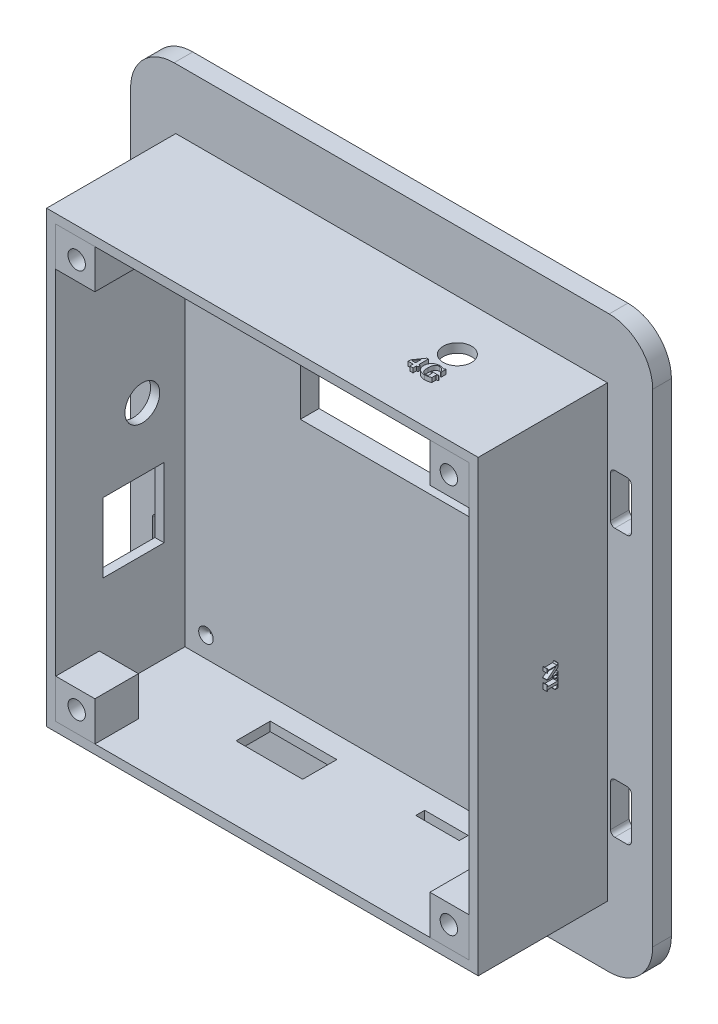
SolidWorks part; units mm, degrees
ref_plane "Front Plane" through (0, 0, 0) normal (0, 0, 1) x (1, 0, 0)
ref_plane "Top Plane" through (0, 0, 0) normal (0, 1, 0) x (1, 0, 0)
ref_plane "Right Plane" through (0, 0, 0) normal (1, 0, 0) x (0, 0, -1)
sketch "Sketch1" plane through (0, 0, 0) normal (0, 0, 1) x (1, 0, 0)
  line L1 (-60, -65.5) -> (60, -65.5)
  line L2 (-60, -65.5) -> (-60, 65.5)
  line L3 (-60, 65.5) -> (60, 65.5)
  line L4 (60, -65.5) -> (60, 65.5)
  line L5 (-60, -65.5) -> (60, 65.5) construction
  line L6 (-60, 65.5) -> (60, -65.5) construction
  point P0 (0, 0)
  dimension "D1" = 120
  dimension "D2" = 131
extrude "Boss-Extrude1" add sketch "Sketch1" along normal blind 4.3
fillet "Fillet1" radius 10 4 edges at (60, 65.5, 2.15) (60, -65.5, 2.15) (-60, -65.5, 2.15) (-60, 65.5, 2.15)
sketch "Sketch4" plane through (0, 0, 0) normal (0, 0, 1) x (1, 0, 0)
  line L0 (50, 65.5) -> (-50, 65.5) construction
  line L1 (-20.98, 43.63) -> (20.89, 43.63)
  line L2 (-20.98, 43.63) -> (-20.98, 9.03)
  line L3 (-20.98, 9.03) -> (20.89, 9.03)
  line L4 (20.89, 43.63) -> (20.89, 9.03)
  line L5 (-20.98, 43.63) -> (20.89, 9.03) construction
  line L6 (-20.98, 9.03) -> (20.89, 43.63) construction
  line L7 (-60, 55.5) -> (-60, -55.5) construction
  point P0 (-0.045, 26.33)
  dimension "D1" = 41.87
  dimension "D2" = 34.6
  dimension "D3" = 21.87
  dimension "D4" = 39.02
extrude "Cut-Extrude1" cut sketch "Sketch4" along normal up to surface (4.3 mm away) up to face at (0, 0, 4.3)
sketch "Sketch5" plane through (0, 0, 0) normal (0, 0, 1) x (1, 0, 0)
  line L0 (-60, 55.5) -> (-60, -55.5) construction
  line L1 (-55, 35) -> (-50.2, 35)
  line L2 (-55, 35) -> (-55, 23.5)
  line L3 (-55, 23.5) -> (-50.2, 23.5)
  line L4 (-50.2, 35) -> (-50.2, 23.5)
  line L5 (-55, 35) -> (-50.2, 23.5) construction
  line L6 (-55, 23.5) -> (-50.2, 35) construction
  line L7 (50, 65.5) -> (-50, 65.5) construction
  line L10 (-20.98, 9.03) -> (-20.98, 43.63) construction
  point P0 (-52.6, 29.25)
  dimension "D1" = 11.5
  dimension "D2" = 4.8
  dimension "D3" = 5
  dimension "D4" = 30.5
  dimension "D5" = 29.22
extrude "Cut-Extrude3" cut sketch "Sketch5" along normal up to surface (4.3 mm away) up to face at (0, 0, 4.3)
sketch "Sketch6" plane through (0, 0, 0) normal (0, 0, 1) x (1, 0, 0)
  line L1 (-55, -26.5) -> (-50.2, -26.5)
  line L2 (-55, -26.5) -> (-55, -38)
  line L3 (-55, -38) -> (-50.2, -38)
  line L4 (-50.2, -26.5) -> (-50.2, -38)
  line L5 (-55, -26.5) -> (-50.2, -38) construction
  line L6 (-55, -38) -> (-50.2, -26.5) construction
  line L7 (-60, 55.5) -> (-60, -55.5) construction
  line L8 (-50.2, 23.5) -> (-55, 23.5) construction
  point P0 (-52.6, -32.25)
  dimension "D1" = 11.5
  dimension "D2" = 4.8
  dimension "D3" = 5
  dimension "D4" = 50
extrude "Cut-Extrude4" cut sketch "Sketch6" along normal up to surface (4.3 mm away) up to face at (-0.045, 26.33, 4.3)
sketch "Sketch7" plane through (0, 0, 0) normal (0, 0, 1) x (1, 0, 0)
  line L1 (50.3, 35) -> (55.1, 35)
  line L2 (50.3, 35) -> (50.3, 23.5)
  line L3 (50.3, 23.5) -> (55.1, 23.5)
  line L4 (55.1, 35) -> (55.1, 23.5)
  line L5 (50.3, 35) -> (55.1, 23.5) construction
  line L6 (50.3, 23.5) -> (55.1, 35) construction
  line L9 (50, 65.5) -> (-50, 65.5) construction
  line L10 (60, -55.5) -> (60, 55.5) construction
  point P0 (52.7, 29.25)
  point P7 (52.7, 35)
  dimension "D1" = 4.8
  dimension "D2" = 11.5
  dimension "D3" = 30.5
  dimension "D4" = 4.9
extrude "Cut-Extrude5" cut sketch "Sketch7" along normal up to surface (4.3 mm away) up to face at (-52.6, 29.25, 4.3)
sketch "Sketch8" plane through (0, 0, 0) normal (0, 0, 1) x (1, 0, 0)
  line L0 (60, -55.5) -> (60, 55.5) construction
  line L1 (50.3, -26.5) -> (55.1, -26.5)
  line L2 (50.3, -26.5) -> (50.3, -38)
  line L3 (50.3, -38) -> (55.1, -38)
  line L4 (55.1, -26.5) -> (55.1, -38)
  line L5 (50.3, -26.5) -> (55.1, -38) construction
  line L6 (50.3, -38) -> (55.1, -26.5) construction
  line L7 (55.1, 23.5) -> (50.3, 23.5) construction
  point P0 (52.7, -32.25)
  dimension "D1" = 4.8
  dimension "D2" = 11.5
  dimension "D3" = 4.9
  dimension "D4" = 50
extrude "Cut-Extrude6" cut sketch "Sketch8" along normal up to surface (4.3 mm away) up to face at (-52.6, -32.25, 4.3)
sketch "Sketch18" plane through (0, 0, 0) normal (0, 0, 1) x (1, 0, 0)
  line L1 (49.5, -51.5) -> (-49.5, -51.5)
  line L2 (49.5, -51.5) -> (49.5, 51.5)
  line L3 (49.5, 51.5) -> (-49.5, 51.5)
  line L4 (-49.5, -51.5) -> (-49.5, 51.5)
  line L5 (49.5, -51.5) -> (-49.5, 51.5) construction
  line L6 (49.5, 51.5) -> (-49.5, -51.5) construction
  point P0 (0, 0)
  dimension "D1" = 99
  dimension "D2" = 103
extrude "Extrude-Thin2" add sketch "Sketch18" along normal blind 34 thin thin type two direction wall 0.1 second wall 2
sketch "Sketch26" plane through (0, 0, 0) normal (0, 0, 1) x (1, 0, 0)
  line L0 (20.89, 43.63) -> (20.89, 9.03) construction
  circle A0 centre (25.89, 44.0116) radius 3.5333
  dimension "D1" = 5
extrude "Boss-Extrude9" add sketch "Sketch26" along normal offset from surface (0.3 mm away) 4 up to face at (0, 0, 4.3)
sketch "Sketch28" plane through (0, 0, 0) normal (1, 0, 0) x (0, 0, -1)
  line L0 (-4.3, 51.6) -> (-4.3, -51.6) construction
  line L1 (-9.1, -10.4) -> (-23.1, -10.4)
  line L2 (-9.1, -10.4) -> (-9.1, -26.4)
  line L3 (-9.1, -26.4) -> (-23.1, -26.4)
  line L4 (-23.1, -10.4) -> (-23.1, -26.4)
  line L5 (-9.1, -10.4) -> (-23.1, -26.4) construction
  line L6 (-9.1, -26.4) -> (-23.1, -10.4) construction
  line L7 (-34, 51.6) -> (-4.3, 51.6) construction
  point P0 (-16.1, -18.4)
  dimension "D1" = 14
  dimension "D2" = 16
  dimension "D3" = 4.8
  dimension "D4" = 62
extrude "Cut-Extrude24" cut sketch "Sketch28" against normal up to surface (49.6 mm away) up to face at (-49.6, 0, 19.15)
sketch "Sketch29" plane through (0, 0, 0) normal (1, 0, 0) x (0, 0, -1)
  line L0 (-4.3, 55.5) -> (-4.3, -55.5) construction
  circle A0 centre (-14.1, 3.9508) radius 4
  dimension "D1" = 9.8
extrude "Cut-Extrude26" cut sketch "Sketch29" against normal up to surface (49.6 mm away) up to face at (-49.6, -18.4, 16.1)
sketch "Sketch30" plane through (0, 0, 0) normal (0, 1, 0) x (1, 0, 0)
  line L0 (49.6, -34) -> (49.6, -4.3) construction
  line L1 (-7.6, -9.3) -> (-22.9, -9.3)
  line L2 (-7.6, -9.3) -> (-7.6, -17.15)
  line L3 (-7.6, -17.15) -> (-22.9, -17.15)
  line L4 (-22.9, -9.3) -> (-22.9, -17.15)
  line L5 (-7.6, -9.3) -> (-22.9, -17.15) construction
  line L6 (-7.6, -17.15) -> (-22.9, -9.3) construction
  line L7 (-49.6, -4.3) -> (49.6, -4.3) construction
  point P0 (-15.25, -13.225)
  dimension "D1" = 15.3
  dimension "D2" = 7.85
  dimension "D3" = 57.2
  dimension "D4" = 5
extrude "Cut-Extrude27" cut sketch "Sketch30" against normal up to surface (51.6 mm away) up to face at (0, -51.6, 19.15)
sketch "Sketch31" plane through (0, 0, 0) normal (0, 1, 0) x (1, 0, 0)
  line L0 (-50, -4.3) -> (50, -4.3) construction
  line L1 (22.6, -9.3) -> (12.6, -9.3)
  line L2 (22.6, -9.3) -> (22.6, -11.35)
  line L3 (22.6, -11.35) -> (12.6, -11.35)
  line L4 (12.6, -9.3) -> (12.6, -11.35)
  line L5 (22.6, -9.3) -> (12.6, -11.35) construction
  line L6 (22.6, -11.35) -> (12.6, -9.3) construction
  line L7 (49.6, -34) -> (49.6, -4.3) construction
  point P0 (17.6, -10.325)
  point P7 (17.6, -9.3)
  point P10 (22.6, -10.325)
  dimension "D1" = 10
  dimension "D2" = 2.05
  dimension "D3" = 5
  dimension "D4" = 27
extrude "Cut-Extrude28" cut sketch "Sketch31" against normal up to surface (51.6 mm away) up to face at (-15.25, -51.6, 13.225)
sketch "Sketch35" plane through (0, -51.6, 0) normal (0, -1, 0) x (-1, 0, 0)
  text T0 "<b>USB</b>" font "Times New Roman" height 4
extrude "Boss-Extrude17" add sketch "Sketch35" along normal blind 1
sketch "Sketch38" plane through (0, -51.6, 0) normal (0, -1, 0) x (-1, 0, 0)
  line L0 (-21.1509, -16.35) -> (-12.6509, -16.35)
  line L1 (-12.6509, -16.35) -> (-12.6509, -26.35)
  line L2 (-12.6509, -26.35) -> (-25.6509, -26.35)
  line L3 (-25.6509, -26.35) -> (-25.6509, -19.35)
  line L4 (-25.6509, -19.35) -> (-21.1509, -16.35)
  line L5 (-22.6, -11.35) -> (-12.6, -11.35) construction
  dimension "D1" = 8.5
  dimension "D2" = 10
  dimension "D3" = 13
  dimension "D4" = 7
  dimension "D5" = 5
extrude "Boss-Extrude23" add sketch "Sketch38" along normal blind 1
sketch "Sketch39" plane through (0, -51.6, 0) normal (0, -1, 0) x (-1, 0, 0)
  text T0 "<b>SIM</b>" font "Times New Roman" height 3.5
extrude "Boss-Extrude30" add sketch "Sketch39" along normal blind 1 separate body
sketch "Sketch54" plane through (0, 0, 0) normal (0, 1, 0) x (1, 0, 0)
  line L2 (50, -4.3) -> (-50, -4.3) construction
  circle A0 centre (26.6908, -15.875) radius 3.25
  dimension "D1" = 11.575
extrude "Cut-Extrude31" cut sketch "Sketch54" along normal up to surface (51.6 mm away) up to face at (0, 51.6, 19.15)
sketch "Sketch55" plane through (0, 51.6, 0) normal (0, 1, 0) x (1, 0, 0)
  text T0 "4G" font "Times New Roman" height 3.5
extrude "Boss-Extrude32" add sketch "Sketch55" along normal blind 1 separate body
sketch "Sketch58" plane through (49.6, 0, 0) normal (1, 0, 0) x (0, 0, -1)
  line L5 (-19.125, 51.6) -> (-19.15, -51.6) construction
  line L6 (-34, -51.6) -> (-4.3, -51.6) construction
  text T0 "<b>NT</b>" font "Times New Roman" height 2.5
extrude "Boss-Extrude34" add sketch "Sketch58" along normal blind 1
sketch "Sketch59" plane through (-49.6, 0, 0) normal (-1, 0, 0) x (0, 0, 1)
  line L0 (27.1425, -51.6) -> (27.1425, 51.6) construction
  line L1 (34, -51.6) -> (4.3, -51.6) construction
  line L2 (34, 51.6) -> (4.3, 51.6) construction
  text T0 "                     LAN" font "Times New Roman" height 3.5
extrude "Boss-Extrude35" add sketch "Sketch59" along normal blind 1
fillet "Fillet4" radius 1 4 edges at (50.3, 35, 2.15) (50.3, 23.5, 2.15) (55.1, 23.5, 2.15) (55.1, 35, 2.15)
fillet "Fillet5" radius 1 4 edges at (50.3, -26.5, 2.15) (50.3, -38, 2.15) (55.1, -38, 2.15) (55.1, -26.5, 2.15)
fillet "Fillet7" radius 1 4 edges at (-55, -38, 2.15) (-50.2, -38, 2.15) (-50.2, -26.5, 2.15) (-55, -26.5, 2.15)
sketch "Sketch61" plane through (0, 0, 4.3) normal (0, 0, 1) x (1, 0, 0)
  line L0 (-47.5, 49.5) -> (-47.5, -49.5) construction
  line L1 (-47.5, -40.5) -> (-38.5, -40.5)
  line L2 (-47.5, -40.5) -> (-47.5, -49.5)
  line L3 (-47.5, -49.5) -> (-38.5, -49.5)
  line L4 (-38.5, -40.5) -> (-38.5, -49.5)
  line L5 (-47.5, -40.5) -> (-38.5, -49.5) construction
  line L6 (-47.5, -49.5) -> (-38.5, -40.5) construction
  line L7 (-47.5, -49.5) -> (47.5, -49.5) construction
  point P0 (-43, -45)
  point P7 (-43, -49.5)
  dimension "D1" = 0
  dimension "D2" = 0
  dimension "D3" = 9
  dimension "D4" = 9
extrude "Boss-Extrude37" add sketch "Sketch61" along normal blind 10 from offset 19.7 separate body
sketch "Sketch62" plane through (0, 0, 4.3) normal (0, 0, 1) x (1, 0, 0)
  line L0 (47.5, 49.5) -> (-47.5, 49.5) construction
  line L1 (38.5, 49.5) -> (47.5, 49.5)
  line L2 (38.5, 49.5) -> (38.5, 40.5)
  line L3 (38.5, 40.5) -> (47.5, 40.5)
  line L4 (47.5, 49.5) -> (47.5, 40.5)
  line L5 (38.5, 49.5) -> (47.5, 40.5) construction
  line L6 (38.5, 40.5) -> (47.5, 49.5) construction
  line L7 (47.5, -49.5) -> (47.5, 49.5) construction
  point P0 (43, 45)
  dimension "D1" = 0
  dimension "D2" = 0
  dimension "D3" = 9
  dimension "D4" = 9
extrude "Boss-Extrude38" add sketch "Sketch62" along normal blind 10 from offset 19.7 separate body
sketch "Sketch63" plane through (0, 0, 4.3) normal (0, 0, 1) x (1, 0, 0)
  line L0 (-47.5, -49.5) -> (47.5, -49.5) construction
  line L1 (38.5, -40.5) -> (47.5, -40.5)
  line L2 (38.5, -40.5) -> (38.5, -49.5)
  line L3 (38.5, -49.5) -> (47.5, -49.5)
  line L4 (47.5, -40.5) -> (47.5, -49.5)
  line L5 (38.5, -40.5) -> (47.5, -49.5) construction
  line L6 (38.5, -49.5) -> (47.5, -40.5) construction
  line L7 (47.5, -49.5) -> (47.5, 49.5) construction
  point P0 (43, -45)
  point P7 (47.5, -45)
  dimension "D1" = 0
  dimension "D2" = 0
  dimension "D3" = 9
  dimension "D4" = 9
extrude "Boss-Extrude39" add sketch "Sketch63" along normal blind 10 from offset 19.7 separate body
sketch "Sketch67" plane through (0, 0, 4.3) normal (0, 0, 1) x (1, 0, 0)
  line L0 (47.5, 49.5) -> (-47.5, 49.5) construction
  line L1 (-47.5, 49.5) -> (-38.5, 49.5)
  line L2 (-47.5, 49.5) -> (-47.5, 40.5)
  line L3 (-47.5, 40.5) -> (-38.5, 40.5)
  line L4 (-38.5, 49.5) -> (-38.5, 40.5)
  line L5 (-47.5, 49.5) -> (-38.5, 40.5) construction
  line L6 (-47.5, 40.5) -> (-38.5, 49.5) construction
  line L7 (-47.5, 49.5) -> (-47.5, -49.5) construction
  point P0 (-43, 45)
  dimension "D1" = 0
  dimension "D2" = 0
  dimension "D3" = 9
extrude "Boss-Extrude40" add sketch "Sketch67" along normal blind 10 from offset 19.7 separate body
sketch "Sketch76" plane through (0, 0, 34) normal (0, 0, 1) x (1, 0, 0)
  point P0 (42.8489, 44.77)
  point P1 (-42.6818, 44.77)
  point P2 (-42.6818, -44.77)
  point P3 (42.8489, -44.77)
hole_wizard "Ø4.0mm Dowel Hole9" positions "3DSketch7" profile "Sketch77" hole size "Ø4.0" standard "ANSI Metric"
sketch3d "3DSketch7"
  point P0 (42.8489, 44.77, 34)
  point P3 (-42.6818, 44.77, 34)
  point P6 (-42.6818, -44.77, 34)
  point P9 (42.8489, -44.77, 34)
sketch "Sketch77" plane through (42.8489, 44.77, 34) normal (1, 0, 0) x (0, -1, 0)
  line L0 (0, 0) -> (0, 30.7017)
  line L1 (0, 30.7017) -> (2, 29.5)
  line L2 (2, 29.5) -> (2, 0)
  line L5 (2, 0) -> (0, 0)
  line L10 (0, 30.7017) -> (-2, 29.5) construction
  line L11 (0, -6.35) -> (0, 107.95) construction
  dimension "Hole Dia." = 4
  dimension "Hole Depth" = 29.5
  dimension "Drill Angle" = 118
